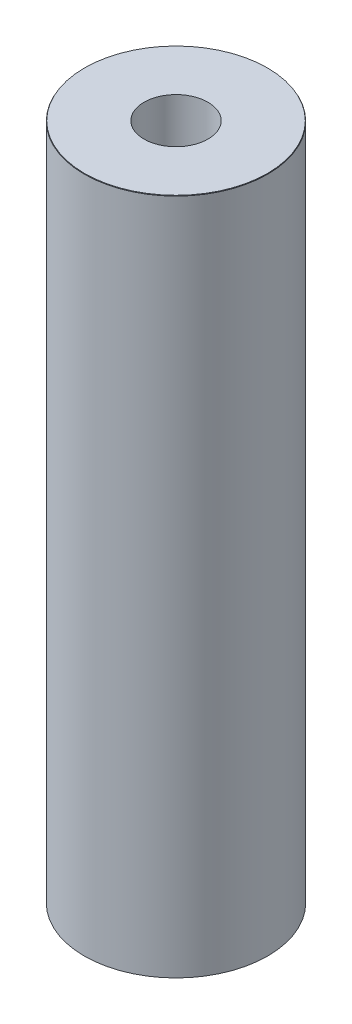
SolidWorks part; units mm, degrees
ref_plane "Front Plane" through (0, 0, 0) normal (0, 0, 1) x (1, 0, 0)
ref_plane "Top Plane" through (0, 0, 0) normal (0, 1, 0) x (1, 0, 0)
ref_plane "Right Plane" through (0, 0, 0) normal (1, 0, 0) x (0, 0, -1)
sketch "Sketch1" plane through (0, 0, 0) normal (0, 1, 0) x (1, 0, 0)
  circle A0 centre (0, 0) radius 47.5
  dimension "SHAFT_OD" = 95
extrude "Boss-Extrude1" add sketch "Sketch1" along normal blind 351.0516
sketch "Sketch2" plane through (0, 0, 0) normal (0, 1, 0) x (1, 0, 0)
  circle A0 centre (0, 0) radius 16.5565
  dimension "BORE_D" = 33.113
extrude "Cut-Extrude1" cut sketch "Sketch2" along normal through all
chamfer "Chamfer1" distance 0.2637 angle 29.387 2 edges at (0, 351.0516, 47.5) (0, 0, 47.5) first distance on face at (0, 351.0516, 47.5) first distance on face at (0, 0, 16.5565)
